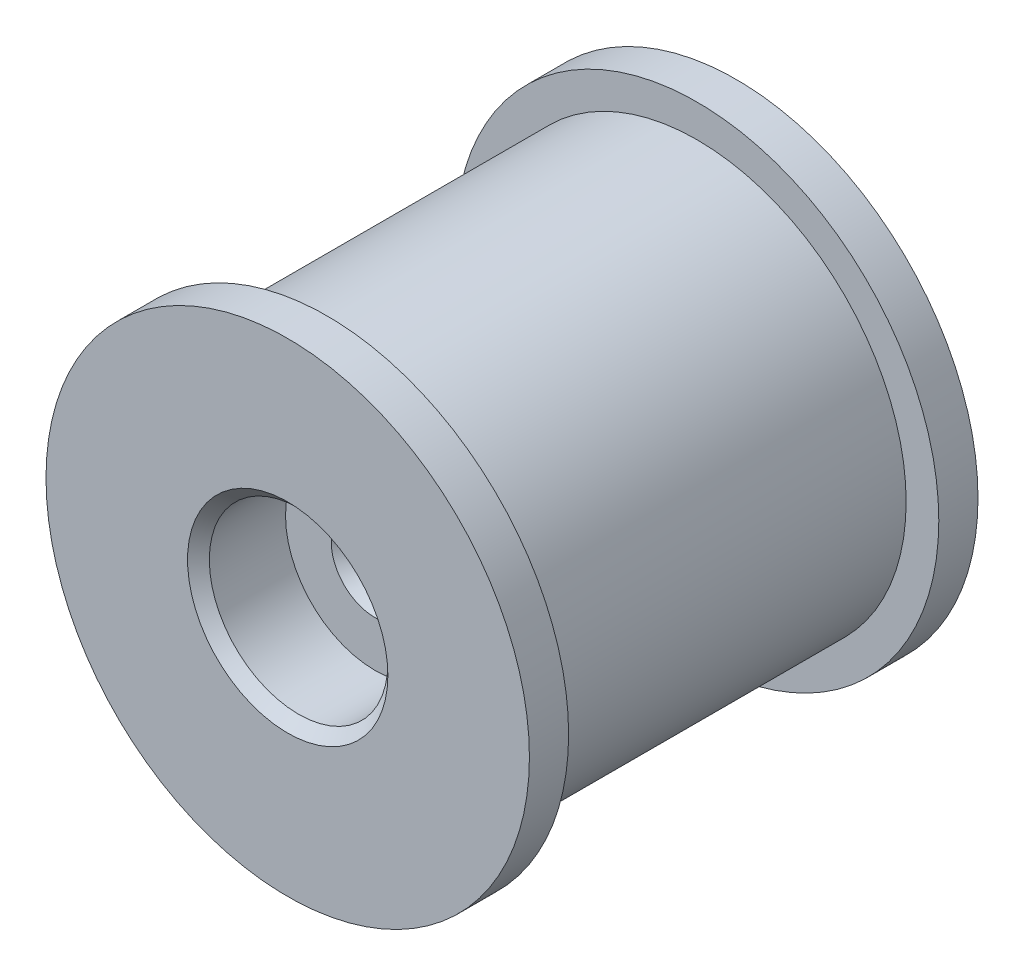
SolidWorks part; units mm, degrees
ref_plane "Ebene vorne" through (0, 0, 0) normal (0, 0, 1) x (1, 0, 0)
ref_plane "Ebene oben" through (0, 0, 0) normal (0, 1, 0) x (1, 0, 0)
ref_plane "Ebene rechts" through (0, 0, 0) normal (1, 0, 0) x (0, 0, -1)
sketch "Skizze1" plane through (0, 0, 0) normal (0, 0, 1) x (1, 0, 0)
  circle A0 centre (0, 0) radius 9.6
  dimension "D1" = 19.2
extrude "Aufsatz-Linear austragen1" add sketch "Skizze1" along normal blind 10.3 and the other way blind 10.3
ref_axis "Rotationsachse" [suppressed] through (0, 0, -9.8) along (0, 0, 1)
sketch "Skizze2" plane through (0, 0, 10.3) normal (0, 0, 1) x (1, 0, 0)
  circle A0 centre (0, 0) radius 11.1
  dimension "D1" = 22.2
extrude "Aufsatz-Linear austragen2" add sketch "Skizze2" against normal blind 1.8
sketch "Skizze3" plane through (0, 0, -10.3) normal (0, 0, -1) x (-1, 0, 0)
  circle A0 centre (0, 0) radius 11.1
  dimension "D1" = 22.2
extrude "Aufsatz-Linear austragen3" add sketch "Skizze3" against normal blind 1.8
sketch "Skizze8" plane through (0, 0, 0) normal (1, 0, 0) x (0, 0, -1)
  line L0 (10.3, 0) -> (10.3, 8)
  line L1 (10.3, -11.1) -> (10.3, 11.1) construction
  line L2 (10.3, 8) -> (8.5, 8)
  line L3 (8.5, 11.1) -> (8.5, -11.1) construction
  line L8 (8.5, 8) -> (-3.7, 6)
  line L9 (-3.7, 6) -> (-3.7, 1.5)
  line L10 (-3.7, 1.5) -> (-6.3, 1.5)
  line L11 (-6.3, 1.5) -> (-6.3, 4.1)
  line L12 (-6.3, 4.1) -> (-10.3, 4.1)
  line L13 (-10.3, 11.1) -> (-10.3, -11.1) construction
  line L14 (-10.3, 4.1) -> (-10.3, 0)
  line L15 (-10.3, 0) -> (10.3, 0)
  dimension "D1" = 8
  dimension "D2" = 4
  dimension "D3" = 4.1
  dimension "D4" = 14
  dimension "D5" = 6
  dimension "D6" = 1.5
revolve "Schnitt-Rotation1" cut sketch "Skizze8" angle 360 about axis through (0, 0, -9.8) along (0, 0, 1)
chamfer "Fase1" distance 0.5 3 edges at (-1.5, 0, 6.3) (-1.5, 0, 3.7) (-4.1, 0, 10.3)
